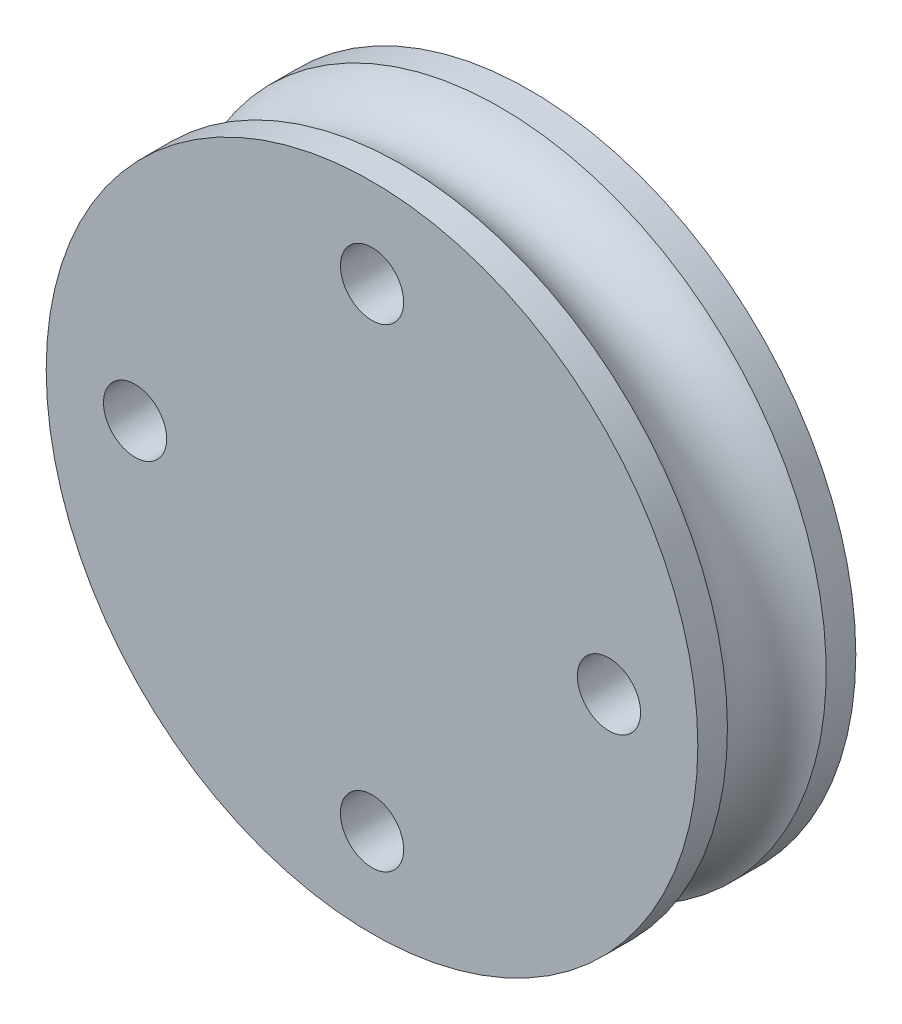
SolidWorks part; units mm, degrees
ref_plane "Ebene vorne" through (0, 0, 0) normal (0, 0, 1) x (1, 0, 0)
ref_plane "Ebene oben" through (0, 0, 0) normal (0, 1, 0) x (1, 0, 0)
ref_plane "Ebene rechts" through (0, 0, 0) normal (1, 0, 0) x (0, 0, -1)
sketch "Skizze2" plane through (0, 0, 0) normal (0, 0, 1) x (1, 0, 0)
  circle A1 centre (6.0006, 0.0004) radius 0.8
  circle A2 centre (0.0006, 6.0004) radius 0.8
  circle A3 centre (-5.9994, 0.0004) radius 0.8
  circle A4 centre (0.0006, -5.9996) radius 0.8
  circle A5 centre (0, 0) radius 8.25
  point P2 (0, 0)
  point P5 (0, 0)
  point P8 (0, 0)
  point P11 (0, 0)
  point P14 (0, 0)
  point P16 (0, 0)
  point P17 (0, -1.079)
  point P18 (0, 0)
  point P19 (0, 0)
  point P20 (0, 0)
  point P21 (0, 0)
  point P22 (0, 0)
  point P23 (0, 0)
  point P24 (0, 0)
  point P25 (0, 0)
  dimension "D1" = 16.5
  dimension "D2" = 1.6
extrude "Aufsatz-Linear austragen1" add sketch "Skizze2" along normal blind 4
sketch "Skizze3" plane through (0, 0, 4) normal (0, 0, 1) x (1, 0, 0)
  circle A0 centre (0.0006, 6.0004) radius 1.9 construction
  circle A1 centre (-5.9994, 0.0004) radius 1.9 construction
  circle A2 centre (0.0006, -5.9996) radius 1.9 construction
  circle A3 centre (6.0006, 0.0004) radius 1.9 construction
  dimension "D1" = 3.8
  dimension "D2" = 3.8
  dimension "D3" = 3.8
  dimension "D4" = 3.8
sketch "Skizze5" plane through (0, 0, 0) normal (1, 0, 0) x (0, 0, -1)
  line L1 (0, 8.25) -> (-4, 8.25) construction
  line L2 (-3.25, 8.25) -> (-0.75, 8.25)
  line L4 (-2, 0) -> (-2, 8.25) construction
  line L5 (8.5813, 0) -> (-8.5813, 0) construction
  line L6 (-3.25, 8.25) -> (-4, 8.25) construction
  line L7 (-0.75, 8.25) -> (0, 8.25) construction
  line L8 (0, 9.075) -> (0, -9.075) construction
  line L9 (-2, 0) -> (-5.4189, 0) construction
  arc A1 (-3.25, 8.25) -> (-0.75, 8.25) centre (-2, 8.8805) ccw
  dimension "D1" = 1.4
  dimension "D2" = 2.5
revolve "Schnitt-Rotation4" cut sketch "Skizze5" angle 360 about L9
